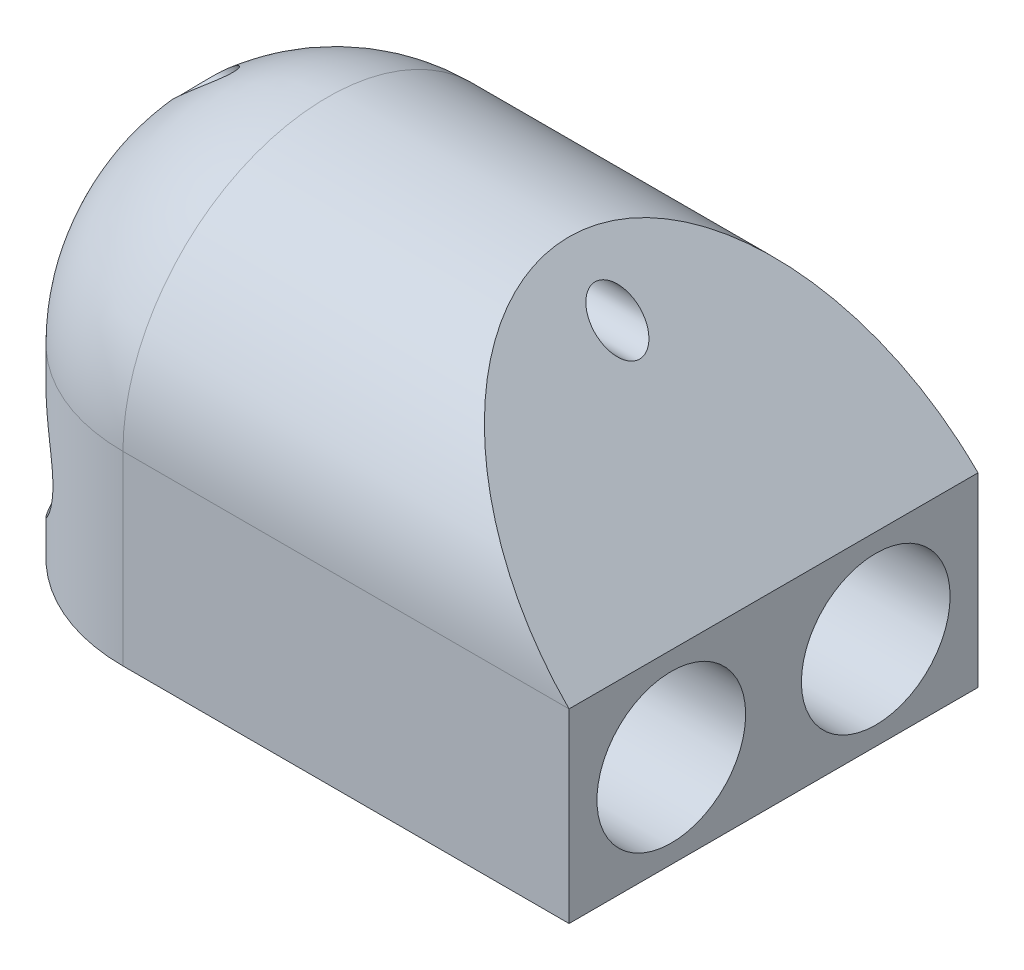
SolidWorks part; units mm, degrees
ref_plane "Front Plane" through (0, 0, 0) normal (0, 0, 1) x (1, 0, 0)
ref_plane "Top Plane" through (0, 0, 0) normal (0, 1, 0) x (1, 0, 0)
ref_plane "Right Plane" through (0, 0, 0) normal (1, 0, 0) x (0, 0, -1)
sketch "Sketch1" plane through (0, 0, 0) normal (0, 1, 0) x (1, 0, 0)
  line L1 (0, 0) -> (-21.59, 0)
  line L2 (0, 0) -> (0, 13.97)
  line L3 (0, 13.97) -> (-21.59, 13.97)
  line L4 (-21.59, 0) -> (-21.59, 13.97)
  dimension "length" = 21.59
  dimension "width" = 13.97
extrude "depth a" add sketch "Sketch1" along normal blind 6.35
sketch "Sketch4" plane through (0, 0, 0) normal (1, 0, 0) x (0, 0, -1)
  line L3 (0, 6.35) -> (13.97, 6.35) construction
  line L4 (0, 6.35) -> (13.97, 6.35)
  arc A0 (0, 6.35) -> (13.97, 6.35) centre (6.985, 6.35) cw
extrude "round extrude" add sketch "Sketch4" against normal up to surface (21.59 mm away) up to face at (-21.59, 3.175, -6.985)
sketch "Sketch5" plane through (0, 0, 0) normal (0, 0, 1) x (1, 0, 0)
  line L0 (0, 6.35) -> (0, 13.335)
  line L1 (0, 13.335) -> (-6.985, 13.335)
  line L2 (0, 13.335) -> (-21.59, 13.335) construction
  line L3 (-6.985, 13.335) -> (0, 6.35)
  line L4 (-10.795, -3.2288) -> (-10.795, 15.9288) construction
  line L9 (-21.59, 6.35) -> (0, 6.35) construction
  point P10 (-10.795, 6.35)
  point P16 (-10.795, 6.35)
  dimension "D1" = 45
extrude "angle cut" cut sketch "Sketch5" against normal through all
sketch "string hole " plane through (0, 0, 0) normal (1, 0, 0) x (0, 0, -1)
  line L0 (6.985, 6.35) -> (6.985, 13.335) construction
  line L1 (13.97, 6.35) -> (0, 6.35) construction
  circle A0 centre (6.985, 11.684) radius 0.762
  arc A1 (13.97, 6.35) -> (0, 6.35) centre (6.985, 6.35) ccw construction
  dimension "D1" = 1.524
  dimension "D2" = 5.334
extrude "string hole cut" cut sketch "string hole " against normal through all
sketch "elastic holes" plane through (0, 0, 0) normal (1, 0, 0) x (0, 0, -1)
  line L1 (13.97, 6.35) -> (0, 6.35) construction
  line L2 (0, 0) -> (13.97, 0) construction
  line L3 (6.985, 0) -> (6.985, 6.35) construction
  line L5 (6.985, 3.175) -> (0, 3.175) construction
  line L7 (0, 6.35) -> (0, 0) construction
  circle A0 centre (3.4925, 3.175) radius 2.54
  circle A1 centre (10.4775, 3.175) radius 2.54
  point P5 (6.985, 6.35)
  point P8 (3.4925, 3.175)
  point P13 (6.985, 3.175)
  point P17 (6.985, 0)
  point P20 (0, 3.175)
  dimension "D1" = 5.08
extrude "elastic hole cut" cut sketch "elastic holes" against normal through all
fillet "Fillet1" radius 6.35 3 edges at (-21.59, 3.175, 0) (-21.59, 3.175, -13.97) (-21.59, 13.335, -6.985)
